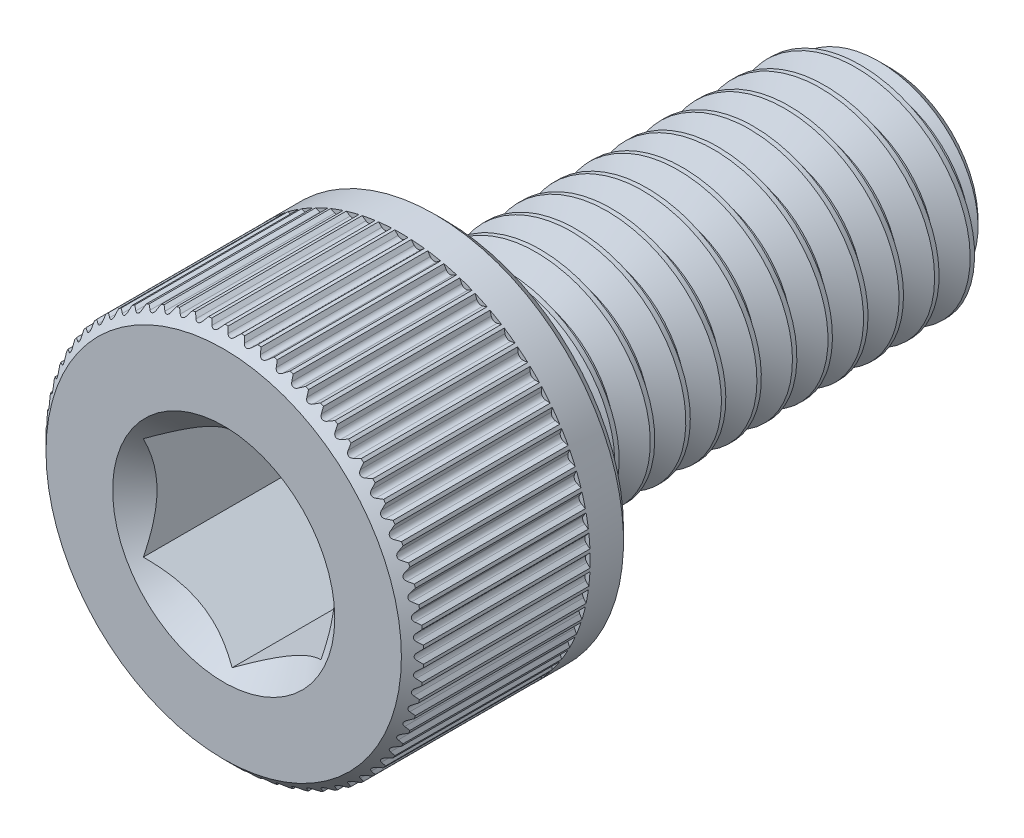
SolidWorks part; units mm, degrees
ref_plane "Front Plane" through (0, 0, 0) normal (0, 0, 1) x (1, 0, 0)
ref_plane "Top Plane" through (0, 0, 0) normal (0, 1, 0) x (1, 0, 0)
ref_plane "Right Plane" through (0, 0, 0) normal (1, 0, 0) x (0, 0, -1)
sketch "Sketch1" plane through (0, 0, 0) normal (1, 0, 0) x (0, 0, -1)
  line L0 (-7.5, 0) -> (7.5, 0) construction
  line L1 (7.5, 0) -> (7.5, 1.9804) construction
  line L2 (7.5, 1.9804) -> (6.9804, 2.5) construction
  line L3 (6.9804, 2.5) -> (6.9, 2.5) construction
  line L4 (6.9, 2.5) -> (-2.5, 2.5) construction
  line L5 (-2.5, 2.5) -> (-2.5, 4.25) construction
  line L6 (-2.5, 4.25) -> (-7.5, 4.25) construction
  line L7 (-7.5, 4.25) -> (-7.5, 0) construction
  line L8 (7.5, 1.9804) -> (7.5, 2.5) construction
  line L9 (7.45, 2.5866) -> (7.85, 1.8938) construction
  line L10 (7.85, 1.8938) -> (8.25, 2.5866) construction
  line L11 (8.25, 2.5866) -> (7.45, 2.5866) construction
  line L12 (7.85, 2.5866) -> (7.85, 2.5) construction
  line L13 (7.85, 1.8938) -> (7.85, 1.9804) construction
  line L14 (7.8, 1.9804) -> (7.9, 1.9804) construction
  line L15 (7.5, 2.5) -> (8.2, 2.5) construction
  line L16 (7.475, 2.5433) -> (8.225, 2.5433) construction
  line L17 (7.5, 0) -> (7.5, -2.5) construction
  line L18 (-2.75, 4.25) -> (-2.5, 4) construction
  line L19 (-7.25, 4.25) -> (-7.5, 4) construction
  line L20 (-2.5, 2.5) -> (-2.5, 0) construction
  line L21 (-2.5, 1.25) -> (0.8333, 1.25) construction
  line L22 (0.8333, 1.25) -> (4.1667, 1.25) construction
  line L23 (4.1667, 1.25) -> (7.5, 1.25) construction
  line L24 (0.8333, 1.25) -> (0.8333, 2.5) construction
  line L25 (0.8333, 2.5) -> (0.8333, 4.25) construction
  line L26 (4.1667, 1.25) -> (4.1667, 4.25) construction
  point P0 (-7.5, 2)
  point P3 (5.5, 2.5)
  point P4 (0, 0)
  point P18 (4.1667, 2.5)
  point P22 (7.85, 1.9804)
  point P24 (6.9, 2.5)
  point P25 (7.85, 2.5)
  point P28 (7.85, 2.5433)
  point P29 (5.5, -2.5)
  point P30 (0.8333, 2.5)
  point P31 (-5, 4.25)
  point P37 (-3.375, 4.25)
  point P38 (-7.125, 4.25)
  point P45 (0.8333, 1.25)
  point P46 (4.1667, 1.25)
  dimension "D7" = 0.25
  dimension "D8" = 0.25
  dimension "D9" = 0.25
  dimension "D10" = 0.125
  dimension "D11" = 0.625
  dimension "Drive Size" = 4
  dimension "Head Diameter" = 8.5
  dimension "Head Height" = 5
  dimension "Thread Pitch" = 0.8
  dimension "Thread Size" = 5
  dimension "Length" = 10
  dimension "D12" = 0.6
  dimension "D4" = 2
  dimension "D3" = 45
sketch "Sketch2" plane through (0, 0, 0) normal (1, 0, 0) x (0, 0, -1)
  line L0 (-7.5, 0) -> (-7.5, 4)
  line L1 (-7.25, 4.25) -> (-2.75, 4.25)
  line L2 (-2.5, 4) -> (-2.5, 2.75)
  line L4 (6.9804, 2.5) -> (7.5, 1.9804)
  line L5 (7.5, 1.9804) -> (7.5, 0)
  line L6 (-2.5, 4.25) -> (-7.5, 4.25) construction
  line L7 (7.5, 0) -> (-7.5, 0)
  line L8 (-7.25, 4.25) -> (-7.5, 4) construction
  line L10 (-7.25, 4.25) -> (-7.5, 4)
  line L14 (-2.75, 4.25) -> (-2.5, 4) construction
  line L16 (-2.75, 4.25) -> (-2.5, 4)
  line L17 (-2.5, 2.5) -> (-2.5, 4.25) construction
  line L19 (-2.25, 2.5) -> (6.9804, 2.5)
  line L20 (6.9, 2.5) -> (-2.5, 2.5) construction
  arc A1 (-2.5, 2.75) -> (-2.25, 2.5) centre (-2.25, 2.75) ccw
  dimension "D3" = 0.25
revolve "Revolve1" add sketch "Sketch2" angle 360 about L7
sketch "Sketch3" plane through (0, 0, 7.5) normal (0, 0, 1) x (1, 0, 0)
  line L1 (2, -1.1547) -> (2, 1.1547)
  line L2 (2, 1.1547) -> (0, 2.3094)
  line L3 (0, 2.3094) -> (-2, 1.1547)
  line L4 (-2, 1.1547) -> (-2, -1.1547)
  line L5 (-2, -1.1547) -> (0, -2.3094)
  line L6 (0, -2.3094) -> (2, -1.1547)
  circle A0 centre (0, 0) radius 2 construction
  circle A1 centre (0, 0) radius 4.25 construction
  circle A2 centre (0, 0) radius 4.25 construction
  circle A3 centre (0, 0) radius 2.3094 construction
  point P13 (0, 0)
extrude "Cut-Extrude1" cut sketch "Sketch3" against normal offset from surface (4 mm away) 1 up to face at (0, 4, 2.5)
sketch "Sketch4" plane through (0, 0, 7.5) normal (0, 0, 1) x (1, 0, 0)
  circle A0 centre (0, 0) radius 2.5
  dimension "D1" = 5
extrude "Cut-Extrude2" cut sketch "Sketch4" against normal up to vertex (2.5 mm away) draft 45 up to point (0, 4.25, 5)
sketch "Sketch11" plane through (0, 0, 0) normal (1, 0, 0) x (0, 0, -1)
  line L0 (-7.5, 0) -> (7.5, 0) construction
  line L1 (-7.5, 0) -> (7.5, 0) construction
  line L2 (-0.625, 0) -> (-0.625, 2.5) construction
  line L3 (6.9, 2.5) -> (-2.5, 2.5) construction
  line L4 (5.625, 0) -> (5.625, 2.5) construction
  line L6 (7.5, 1.9804) -> (7.5, 2.5) construction
  point P2 (-0.625, 0)
  point P3 (5.625, 0)
  dimension "D1" = 1.875
  dimension "D2" = 1.875
sketch "Sketch6" plane through (0, 0, -7.5) normal (0, 0, -1) x (-1, 0, 0)
  circle A0 centre (0, 0) radius 2.5
curve "Helix/Spiral1" pitch 0.8 height 10.8 radius 2.5 centre (0, 0, -7.5) axis (0, 0, 1) start towards (0, 1, 0)
sketch "Sketch10" plane through (0, 0, 0) normal (1, 0, 0) x (0, 0, -1)
  line L0 (-2.25, -4.25) -> (-2.25, 4.25)
  line L5 (-7.5, 0) -> (7.5, 0) construction
  line L6 (-2.25, 2.5) -> (-2.25, -2.5) construction
  point P3 (-2.25, 0)
split "Split1" trim tools "Sketch10" bodies to split 106 resulting bodies 114 115
sketch "Sketch7" plane through (0, 0, 0) normal (1, 0, 0) x (0, 0, -1)
  line L0 (7.475, 2.5433) -> (8.225, 2.5433)
  line L1 (8.225, 2.5433) -> (7.9, 1.9804)
  line L2 (7.9, 1.9804) -> (7.8, 1.9804)
  line L3 (7.8, 1.9804) -> (7.475, 2.5433)
sweep "Cut-Sweep1" cut profiles "Sketch7" path "Helix/Spiral1" align with end faces yes
sketch "Sketch8" plane through (0, 0, 0) normal (1, 0, 0) x (0, 0, -1)
  line L0 (-2.5, 0) -> (-2.5, 2.5)
  line L1 (-2.25, -2.5) -> (-2.25, 2.5) construction
  line L2 (-2.5, 2.5) -> (-2.25, 2.5)
  line L4 (-2.25, 2.5) -> (-0.8066, 0)
  line L5 (-0.8066, 0) -> (-2.5, 0)
  line L6 (6.9, 2.5) -> (-2.5, 2.5) construction
  line L7 (-7.5, 0) -> (7.5, 0) construction
  dimension "D1" = 60
revolve "Revolve2" add sketch "Sketch8" angle 360 about L5
ref_plane "Plane1" through (0, 0, 7.5) normal (0, 0, 1) x (1, 0, 0)
sketch "Sketch12" plane through (0, 0, 7.5) normal (0, 0, 1) x (1, 0, 0)
  line L0 (0, 0) -> (0.1483, 4.2474) construction
  line L1 (0, 0) -> (-0.1483, 4.2474) construction
  line L2 (0, 4.1437) -> (0, 4.3563) construction
  line L3 (-0.2572, 4.3563) -> (0.2572, 4.3563)
  line L4 (-0.2572, 4.3563) -> (-0.0762, 4.1753)
  line L5 (0.0762, 4.1753) -> (0.2572, 4.3563)
  circle A0 centre (0, 0) radius 4.25 construction
  arc A1 (-0.0762, 4.1753) -> (0.0762, 4.1753) centre (0, 4.2516) ccw
  point P9 (0, 4.3563)
  point P13 (0, 4.25)
  dimension "D1" = 4
  dimension "D2" = 0.1063
extrude "Cut-Extrude3" cut sketch "Sketch12" against normal blind 4
pattern_circular "CirPattern1" count 72 over 360 about axis through (0, 0, 7.5) along (0, 0, -1) of "Cut-Extrude3"
equation "\"D2@Sketch1\" = \"Thread Pitch@Sketch1\" / 8"
equation "\"D4@Helix/Spiral1\" = \"Thread Pitch@Sketch1\""
equation "\"D7@Sketch1\" = \"Head Height@Sketch1\" * .05"
equation "\"D8@Sketch1\"=\"D7@Sketch1\""
equation "\"D9@Sketch1\"=\"D7@Sketch1\""
equation "\"D10@Sketch1\"=\"D7@Sketch1\"/2"
equation "\"D11@Sketch1\"=\"D10@Sketch1\"*5"
equation "\"D4@Sketch1\"=\"Thread Pitch@Sketch1\"*2.5"
equation "\"D12@Sketch1\"=\"Thread Pitch@Sketch1\"*.75"
equation "\"D3@Helix/Spiral1\"=\"Length@Sketch1\"+\"Thread Pitch@Sketch1\""
equation "\"D3@Sketch2\" = \"Thread Size@Sketch1\" * 0.05"
equation "\"D1@Sketch11\"=\"Length@Sketch1\"*0.1875"
equation "\"D2@Sketch11\"=\"D1@Sketch11\""
equation "\"D2@Sketch12\"=\"Head Diameter@Sketch1\"*.0125"
equation "\"D1@Cut-Extrude3\"=\"Head Height@Sketch1\"*.8"
equation "\"D1@CirPattern1\"=\"D3@CirPattern1\"/(1.25*\"D1@Sketch12\")"
equation "\"D1@Sketch4\"=\"Drive Size@Sketch1\"*1.25"
